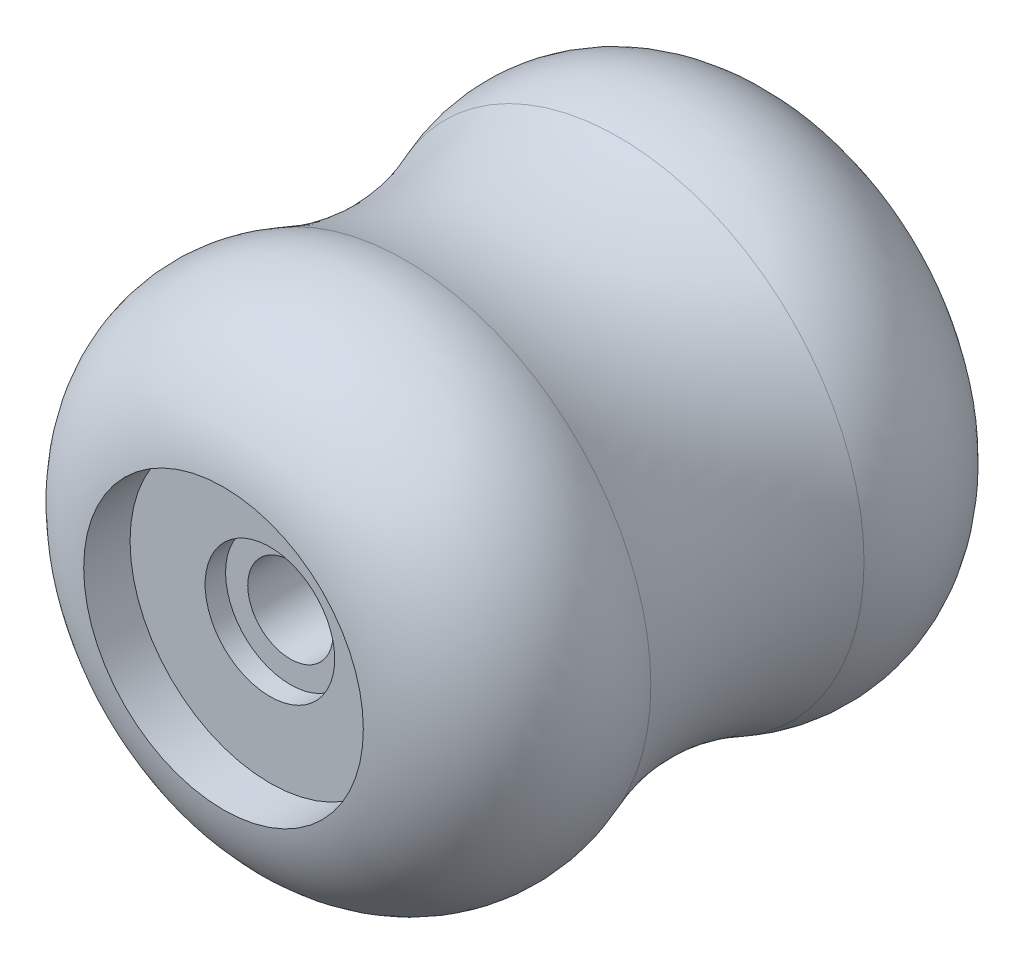
SolidWorks part; units mm, degrees
ref_plane "Front" through (0, 0, 0) normal (0, 0, 1) x (1, 0, 0)
ref_plane "Top" through (0, 0, 0) normal (0, 1, 0) x (1, 0, 0)
ref_plane "Right" through (0, 0, 0) normal (1, 0, 0) x (0, 0, -1)
sketch "Sketch1" plane through (0, 0, 0) normal (0, 1, 0) x (1, 0, 0)
  line L0 (0, -21.59) -> (0, 21.59)
  line L1 (0, 21.59) -> (-14.9364, 21.59)
  line L2 (0, -21.59) -> (-14.9364, -21.59)
  line L3 (-20.2585, -11.7764) -> (-14.9364, -21.59)
  arc A3 (-14.9364, 21.59) -> (-20.2585, 11.7764) centre (-14.9364, 15.24) ccw
  arc A4 (-14.9364, -21.59) -> (-20.2585, -11.7764) centre (-14.9364, -15.24) cw
  circle A6 centre (-35.814, 0) radius 19.05
  arc A7 (-20.2585, 11.7764) -> (-20.2585, -11.7764) centre (-38.354, 0) cw
  arc A8 (-18.2767, -7.939) -> (-17.7687, -16.3673) centre (-8.9951, -11.6092) ccw
  arc A9 (-17.7687, -16.3673) -> (-8.9951, -21.59) centre (-8.9951, -11.6092) ccw
  arc A10 (-8.9951, 21.59) -> (-18.2767, 7.939) centre (-8.9951, 11.6092) ccw
  point P0 (-16.764, 0)
  point P4 (0, 0)
  point P7 (-16.764, 0)
  point P13 (-16.764, 0)
  point P24 (-18.2767, 7.939)
  dimension "D4" = 38.1
  dimension "D3" = 21.59
  dimension "D5" = 6.35
  dimension "D1" = 43.18
  dimension "D6" = 35.814
revolve "Revolve1" add sketch "Sketch1" angle 360 about L0 region at (-8.7398, 0, 0)
sketch "Sketch2" plane through (0, 0, -21.59) normal (0, 0, -1) x (-1, 0, 0)
  circle A0 centre (0, 0) radius 10.414
  circle A1 centre (0, 0) radius 4.826
  circle A2 centre (0, 0) radius 3.175
  point P5 (0, 0)
  circle M5 centre (0, 0) radius 8.9951
  dimension "D1" = 20.828
  dimension "D2" = 9.652
  dimension "D3" = 6.35
extrude "Cut-Extrude1" cut sketch "Sketch2" against normal blind 3.556 contours A0 A1 | A1 M5 region at (10.1194, 0, -21.59) region at (8.7407, 0, -21.59)
extrude "Cut-Extrude2" cut sketch "Sketch2<3>" against normal blind 5.08 contours A1 A2 region at (4.6895, 0, -21.59)
sketch "Sketch2<3>" plane through (0, 0, -21.59) normal (0, 0, -1) x (-1, 0, 0) same geometry as "Sketch2"
extrude "Cut-Extrude3" cut sketch "Sketch2<4>" against normal through all contours A2 region at (0, 0, -21.59)
sketch "Sketch2<4>" plane through (0, 0, -21.59) normal (0, 0, -1) x (-1, 0, 0) same geometry as "Sketch2"
mirror "Mirror1" about plane through (0, 0, 0) normal (0, 0, 1) of "Cut-Extrude1", "Cut-Extrude2"
equation "\"D3@Sketch1\"=(\"D4@Sketch1\"/2) + .1"
